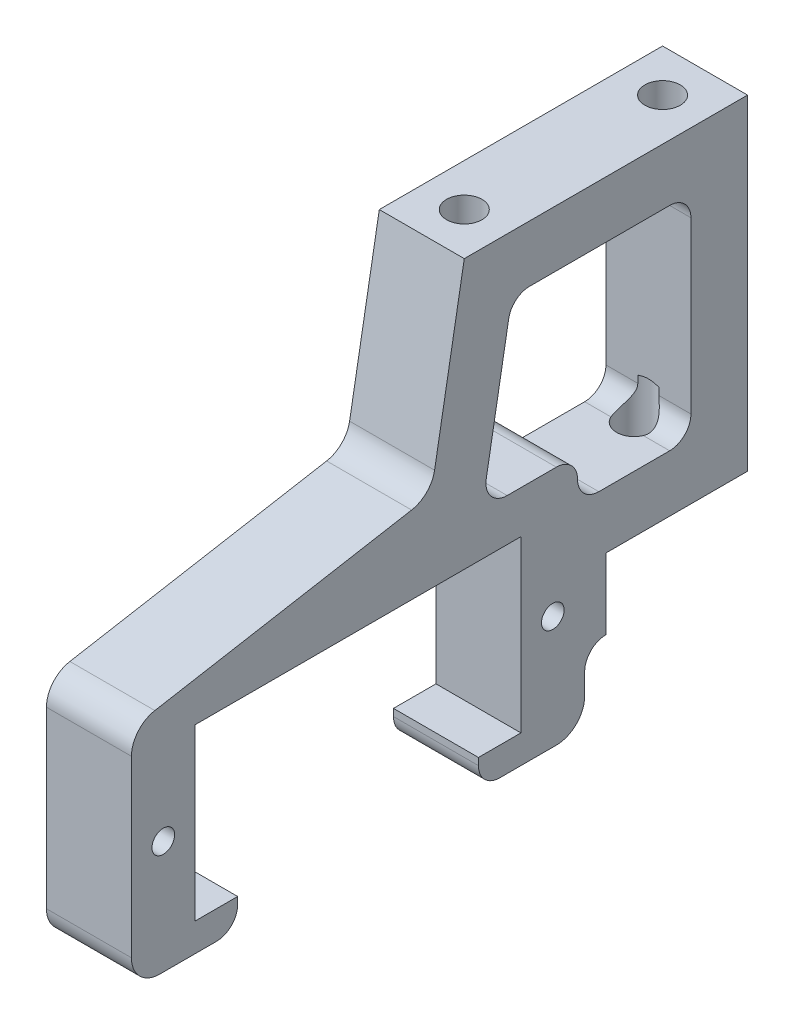
SolidWorks part; units mm, degrees
material "1060 Alloy"
ref_plane "Front Plane" through (0, 0, 0) normal (0, 0, 1) x (1, 0, 0)
ref_plane "Top Plane" through (0, 0, 0) normal (0, 1, 0) x (1, 0, 0)
ref_plane "Right Plane" through (0, 0, 0) normal (1, 0, 0) x (0, 0, -1)
sketch "Sketch2" plane through (0, 0, 0) normal (1, 0, 0) x (0, 0, -1)
  line L0 (-19, -33) -> (-11.5, -33)
  line L1 (-20, 0) -> (-22.3397, -13.2689)
  line L2 (-22.3397, -13.2689) -> (-43.5, -17)
  line L3 (-10, -28) -> (-10, -23)
  line L4 (-10, -23) -> (0, -23)
  line L5 (-36, -33) -> (-36, -31)
  line L6 (-36, -31) -> (-39, -31)
  line L7 (-19, -33) -> (-19, -31)
  line L8 (0, -23) -> (0, 0)
  line L9 (-43.5, -33) -> (-36, -33)
  line L10 (-16, -19) -> (-16, -31)
  line L11 (-39, -19) -> (-16, -19)
  line L12 (-39, -31) -> (-39, -19)
  line L13 (-19, -31) -> (-16, -31)
  line L14 (-43.5, -17) -> (-43.5, -33)
  line L15 (-11.5, -33) -> (-11.5, -28)
  line L16 (0, 0) -> (-20, 0)
  line L17 (-11.5, -28) -> (-10, -28)
  circle A2 centre (-41.25, -25) radius 0.8
  circle A3 centre (-13.75, -25) radius 0.8
  dimension "D8" = 20
  dimension "D9" = 6
  dimension "D11" = 1.6
  dimension "D1" = 19
  dimension "D2" = 39
  dimension "D3" = 3
  dimension "D4" = 2.25
  dimension "D5" = 2.25
  dimension "D6" = 4.5
  dimension "D7" = 10
  dimension "D10" = 23
  dimension "D12" = 100
  dimension "D13" = 100
  dimension "D14" = 2
  dimension "D15" = 23
  dimension "D16" = 12
  dimension "D17" = 2
  dimension "D18" = 4.5
  dimension "D19" = 5
extrude "Boss-Extrude1" add sketch "Sketch2" along normal blind 6
fillet "Fillet1" radius 1.5 3 edges at (3, -33, 19) (3, -33, 36) (3, -28, 11.5)
fillet "Fillet2" radius 2 4 edges at (3, -13.2689, 22.3397) (3, -17, 43.5) (3, -33, 43.5) (3, -33, 11.5)
sketch "Sketch3" plane through (6, 0, 0) normal (1, 0, 0) x (0, 0, -1)
  line L0 (-16.6436, -4) -> (-4, -4)
  line L1 (-4, -4) -> (-4, -19)
  line L2 (-4, -19) -> (-12, -19)
  line L3 (-12, -19) -> (-12, -16)
  line L4 (-12, -16) -> (-18.7595, -16)
  line L5 (-18.7595, -16) -> (-16.6436, -4)
  line L6 (-20, 0) -> (-22.0965, -11.8897) construction
  line L7 (0, 0) -> (-20, 0) construction
  line L8 (0, -23) -> (0, 0) construction
  line L9 (-10, -23) -> (0, -23) construction
  line L10 (-16, -19) -> (-16, -31) construction
  line L11 (-39, -19) -> (-16, -19) construction
  dimension "D1" = 4
  dimension "D2" = 4
  dimension "D3" = 4
  dimension "D4" = 4
  dimension "D5" = 4
  dimension "D6" = 3
extrude "Cut-Extrude1" cut sketch "Sketch3" against normal up to next
fillet "Fillet3" radius 1.5 6 edges at (3, -19, 4) (3, -19, 12) (3, -16, 12) (3, -4, 4) (3, -4, 16.6436) (3, -16, 18.7595)
hole_wizard "Tap Drill for M3 Tap1" positions "3DSketch1" profile "Sketch4" hole size "M3" standard "ISO"
sketch3d "3DSketch1"
  line L0 (6, -23, 0) -> (0, -23, 0) construction
  line L1 (0, -23, 10) -> (0, -23, 0) construction
  line L2 (6, 0, 0) -> (0, 0, 0) construction
  line L3 (6, 0, 20) -> (0, 0, 20) construction
  line L4 (6, 0, 0) -> (6, 0, 20) construction
  point P0 (3, 0, 17)
  point P2 (3, 0, 3)
  point P4 (3, -23, 5)
  dimension "D1" = 5
  dimension "D2" = 3
  dimension "D3" = 3
  dimension "D4" = 3
  dimension "D5" = 3
sketch "Sketch4" plane through (3, 0, 17) normal (1, 0, 0) x (0, 0, 1)
  line L0 (0, 0) -> (0, 6.7511)
  line L1 (0, 6.7511) -> (1.25, 6)
  line L2 (1.25, 6) -> (1.25, 0)
  line L5 (1.25, 0) -> (0, 0)
  line L10 (0, 6.7511) -> (-1.25, 6) construction
  line L11 (0, -6.35) -> (0, 107.95) construction
  dimension "Hole Dia." = 2.5
  dimension "Hole Depth" = 6
  dimension "Drill Angle" = 118
